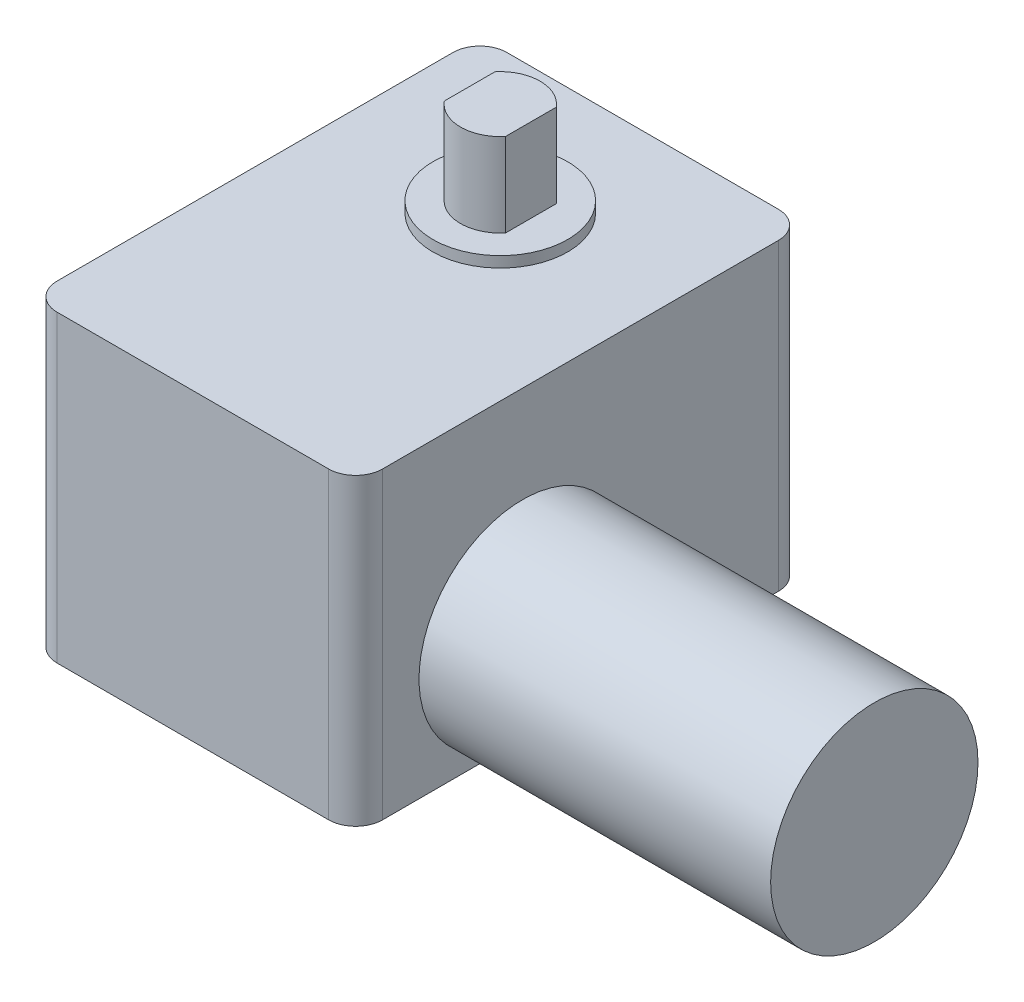
SolidWorks part; units mm, degrees
material "Delrin 2700 NC010, Low Viscosity Acetal Copolymer (SS)"
ref_plane "Front Plane" through (0, 0, 0) normal (0, 0, 1) x (1, 0, 0)
ref_plane "Top Plane" through (0, 0, 0) normal (0, 1, 0) x (1, 0, 0)
ref_plane "Right Plane" through (0, 0, 0) normal (1, 0, 0) x (0, 0, -1)
sketch "Sketch2" plane through (0, 0, 0) normal (0, 1, 0) x (1, 0, 0)
  line L0 (0, 0) -> (0, 16.68)
  line L1 (0, 0) -> (12.07, 0)
  line L2 (0, 16.68) -> (12.07, 16.68)
  line L3 (12.07, 0) -> (12.07, 16.68)
  line L4 (12.07, 2.35) -> (12.07, 10.04)
  line L5 (12.07, 2.35) -> (25.11, 2.35)
  line L7 (25.11, 2.35) -> (25.11, 6.195)
  line L8 (4.8983, 12.34) -> (4.8983, 10.46)
  line L9 (7.1717, 12.34) -> (7.1717, 10.46)
  line L10 (25.11, 6.195) -> (12.07, 6.195)
  circle A0 centre (6.035, 11.4) radius 2.5
  arc A1 (4.8983, 10.46) -> (7.1717, 10.46) centre (6.035, 11.4) ccw
  arc A2 (7.1717, 12.34) -> (4.8983, 12.34) centre (6.035, 11.4) ccw
  point P11 (6.035, 16.68)
  dimension "D7" = 5
  dimension "D8" = 2.95
  dimension "D1" = 12.07
  dimension "D2" = 16.68
  dimension "D3" = 2.35
  dimension "D4" = 3.845
  dimension "D5" = 25.11
  dimension "D6" = 11.4
  dimension "D9" = 1.88
revolve "Revolve1" add sketch "Sketch2" angle 360 about L10 region at (18.59, 0, -4.2725)
extrude "Boss-Extrude1" add sketch "Sketch2<5>" against normal blind 3.845 contours L1 L3 L4 L2 L0 A0 | A0 A2 L9 A1 L8 | L9 A2 L8 A1 region at (6.035, 0, -8.0093) region at (6.035, 0, -11.4) region at (3.6057, 0, -11.4)
sketch "Sketch2<5>" plane through (0, 0, 0) normal (0, 1, 0) x (1, 0, 0) same geometry as "Sketch2"
extrude "Boss-Extrude2" add sketch "Sketch2<6>" along normal blind 7.425 contours L1 L3 L4 L2 L0 A0 region at (6.035, 0, -8.0093)
sketch "Sketch2<6>" plane through (0, 0, 0) normal (0, 1, 0) x (1, 0, 0) same geometry as "Sketch2"
extrude "Boss-Extrude3" add sketch "Sketch2<7>" along normal blind 7.825 contours A0 A2 L9 A1 L8 region at (3.6057, 0, -11.4)
sketch "Sketch2<7>" plane through (0, 0, 0) normal (0, 1, 0) x (1, 0, 0) same geometry as "Sketch2"
extrude "Boss-Extrude4" add sketch "Sketch2<8>" along normal blind 10.925 contours L9 A2 L8 A1 region at (6.035, 0, -11.4)
sketch "Sketch2<8>" plane through (0, 0, 0) normal (0, 1, 0) x (1, 0, 0) same geometry as "Sketch2"
fillet "Fillet1" radius 1 4 edges at (0, 1.79, 0) (12.07, 1.79, 0) (12.07, 1.79, -16.68) (0, 1.79, -16.68)
equation "\"whitemotordepth\"=11.27mm"
equation "\"D1@Boss-Extrude2\"=\"whitemotordepth\" - \"whitemotorbackdepth\""
equation "\"whitemotorbackdepth\"=3.845mm"
equation "\"D1@Boss-Extrude1\"=\"whitemotorbackdepth\""
equation "\"D1@Boss-Extrude3\"=\"whitemotordepth\"-\"whitemotorbackdepth\"+.4"
equation "\"whitemotoraxledepth\" = 3.5mm"
equation "\"D1@Boss-Extrude4\"=\"whitemotoraxledepth\"+\"whitemotordepth\"-\"whitemotorbackdepth\""
equation "\"whitemotoraxleoffset\"=11.4mm"
equation "\"D6@Sketch2\"=\"whitemotoraxleoffset\""
equation "\"whitemotorwidth\"=12.07mm"
equation "\"D1@Sketch2\"=\"whitemotorwidth\""
equation "\"whitemotorheight\"=16.68mm"
equation "\"D2@Sketch2\"=\"whitemotorheight\""
equation "\"whitemotorcylinderlength\" =13.04mm"
equation "\"D5@Sketch2\"=\"whitemotorcylinderlength\"+\"whitemotorwidth\""
equation "\"whitemotorcylinderradius\"=3.845mm"
equation "\"D4@Sketch2\"=\"whitemotorcylinderradius\""
equation "\"whitemotorcylinderoffset\"=2.35mm"
equation "\"D3@Sketch2\"=\"whitemotorcylinderoffset\""
equation "\"whitemotorcutoutlength\"=1.88mm"
equation "\"D9@Sketch2\"=\"whitemotorcutoutlength\""
equation "\"whitemotorouterrad\"=5mm"
equation "\"D7@Sketch2\"=\"whitemotorouterrad\""
equation "\"whitemotorinnerrad\"=2.95mm"
equation "\"D8@Sketch2\"=\"whitemotorinnerrad\""
equation "\"CageLeftBottomEdge\"=22.11mm"
equation "\"CageLeftTopEdge\"=22.11mm"
equation "\"CageRightBottomEdge\"=21.63mm"
equation "\"CageRightTopEdge\"=21.63mm"
equation "\"CageHeight\"=86.04mm"
equation "\"CageLength\"=73.76mm"
equation "\"CageTopScrewClearance\"=10mm"
equation "\"CageBottomScrewClearance\"=25mm"
equation "\"CageLeftTopDepth\"= 11.65mm"
equation "\"CageLeftBottomDepth\"=11.11mm"
equation "\"CageLeftTopHeight\"=8.56175mm"
equation "\"CageLeftBottomHeight\"=16mm"
equation "\"CageRightTopDepth\"= 11.05mm"
equation "\"CageRightBottomDepth\"=10.58mm"
equation "\"CageRightTopHeight\"=9.6mm"
equation "\"CageRightBottomHeight\"=15.49mm"
equation "\"CageLeftTopChannelDepth\"=2.41908mm"
equation "\"CageLeftBottomChannelDepth\"=2.588mm"
equation "\"CageLeftChannelHeight\"=11.7mm"
equation "\"CageRightTopChannelDepth\"=2.32mm"
equation "\"CageRightBottomChannelDepth\"=2.318mm"
equation "\"CageRightChannelHeight\"=10mm"
equation "\"CageChanRelHeight\"=23.99mm"
equation "\"CageChanRelDepth\"=5.492mm"
equation "\"CageChamberRadius\"=16.261mm"
equation "\"CageScrewDiameter\"=4.8mm"
equation "\"CageSetScrewDiameter\"=3.5mm"
equation "\"CageAxleRadius\"=6.639mm"
equation "\"CageAxleKeyHeight\"=1.619mm"
equation "\"CageAxleKeyWidth\"=2.662mm"
equation "\"CageHoseWindowWidth\"=16.29mm"
equation "\"CageHoseWindowHeight\"=26.5mm"
equation "\"CageHoseWindow-Edge\"=8.89mm"
equation "\"CageScrew-VerticalEdge\"=5.0mm"
equation "\"CageScrew-HorizontalEdge\"=7.5mm"
equation "\"CageScrew-HoseCornerScrewEdge\"=4.45mm"
equation "\"CageAxle-BottomEdge\"=56.05mm"
equation "\"CageAxle-FrontEdge\"=46.03mm"
equation "\"CageBackSetScrew-Axle\"=40mm"
equation "\"CageFrontSetScrew-Axle\"=22mm"
equation "\"CageVelocityWindow-BackEdge\"=34.8mm"
equation "\"CageVelocityWindow-BottomEdge\"=27.55mm"
equation "\"CageVelocityWindowHeight\"=22.29mm"
equation "\"CageVelocityWindowWidth\"=12.61mm"
equation "\"TriggerSlot-BottomEdge\"=6.35mm"
equation "\"TriggerSlot-FrontEdge\"=15mm"
equation "\"TriggerSlotSize\"=6.7mm"
equation "\"TriggerRackOffset\"=.236224in"
equation "\"TriggerSlotSizeInt\"=.25in"
equation "\"MotorMountLegLength\"=.25in"
equation "\"GearOffset\"=.264907in"
equation "\"TriggerSlotSpacing\"=.25in"
equation "\"TGMGearFaceDiameter\"=24.40mm"
equation "\"TGMCylinderLength\"=15.00mm"
equation "\"TGMScrewHole-Center\"=8.70mm"
equation "\"TGMScrewHoleDiameter\"=5.04mm"
equation "\"TGMCenterHoleDiameter\"=9.50mm"
equation "\"TGMShaftCollarSideLength\"=19.00mm"
equation "\"TGMShaftCollarDockingDepth\"=7.00mm"
equation "\"TriggerMiniSlotWidth\"=3.5mm"
equation "\"TriggerRackWidth\"=6.5mm"
equation "\"elasticracklength\"=2in"
equation "\"elasticrackpegsize\"=.25in"
equation "\"elasticrackpegbuffer\"=.125in"
equation "\"elasticrackpegspacing\"=1.76476378in"
equation "\"elasticbaybuffer\"=.25in"
equation "\"elasticdepth\"=.125in"
equation "\"elasticbaydepth\"=.75in"
equation "\"motormountwidth\"=12mm"
equation "\"motormountcornerfillet\"=3mm"
equation "\"pandiscradius\"=14in"
equation "\"towermaterialwidth\"=.25in"
equation "\"towerslotlength\"=.5in"
equation "\"towermarkerspace\"=5in"
equation "\"towerslothorizoffset\"=1in"
equation "\"towerslothorizspacing\"=2in"
equation "\"towerslotvertoffset\"=3in"
equation "\"towerslotvertspacing\"=2in"
equation "\"towerheight\"=12in"
equation "\"towerupslot\"=1in"
equation "\"toweraxle\"=.5in"
equation "\"towerplatslotoffset\"=1.5in"
equation "\"towermotorpanelheight\"=10in"
equation "\"towerplatdepth\"=2in"
equation "\"stepperouterrad\"=10mm"
equation "\"stepperscrewsize\"=3.45mm"
equation "\"stepperscrewc2c\"=49.5mm"
equation "\"stepperdepthoffset\"=24mm"
equation "\"stepperhorizoffset\"=22.91mm"
